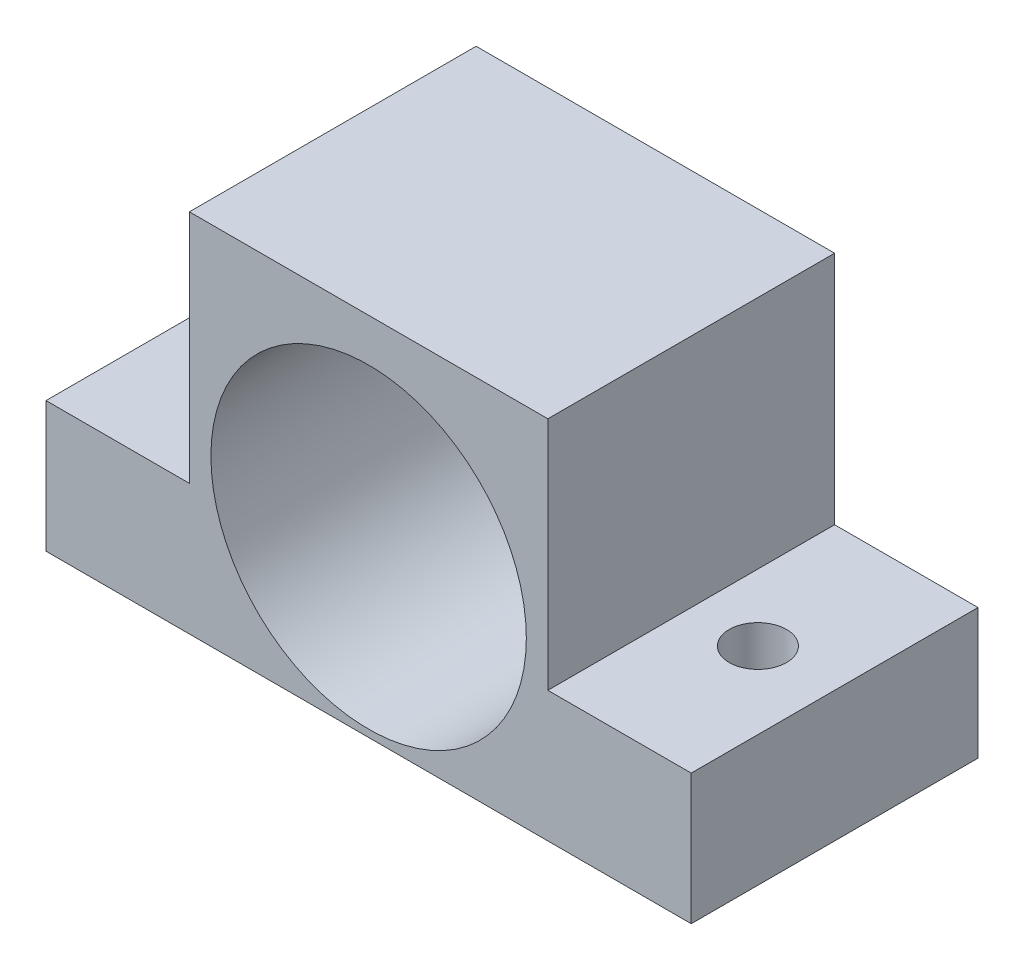
SolidWorks part; units mm, degrees
material "ABS"
ref_plane "Front Plane" through (0, 0, 0) normal (0, 0, 1) x (1, 0, 0)
ref_plane "Top Plane" through (0, 0, 0) normal (0, 1, 0) x (1, 0, 0)
ref_plane "Right Plane" through (0, 0, 0) normal (1, 0, 0) x (0, 0, -1)
sketch "Sketch1" plane through (0, 0, 0) normal (0, 0, 1) x (1, 0, 0)
  line L0 (185.6419, -17.5) -> (-64.3581, -17.5) construction
  line L1 (-11.4483, 8) -> (13.5517, 8)
  line L2 (-11.4483, 8) -> (-11.4483, -17.5)
  line L3 (-11.4483, -17.5) -> (13.5517, -17.5)
  line L4 (13.5517, 8) -> (13.5517, -17.5)
  line L5 (-11.4483, 8) -> (13.5517, -17.5) construction
  line L6 (-11.4483, -17.5) -> (13.5517, 8) construction
  line L7 (13.5517, -17.5) -> (23.5517, -17.5)
  line L8 (13.5517, -17.5) -> (13.5517, -8.4)
  line L9 (13.5517, -8.4) -> (23.5517, -8.4)
  line L10 (23.5517, -17.5) -> (23.5517, -8.4)
  line L11 (13.5517, -17.5) -> (23.5517, -8.4) construction
  line L12 (13.5517, -8.4) -> (23.5517, -17.5) construction
  line L13 (-11.4483, -17.5) -> (-21.4483, -17.5)
  line L14 (-11.4483, -17.5) -> (-11.4483, -8.4)
  line L15 (-11.4483, -8.4) -> (-21.4483, -8.4)
  line L16 (-21.4483, -17.5) -> (-21.4483, -8.4)
  line L17 (-11.4483, -17.5) -> (-21.4483, -8.4) construction
  line L18 (-11.4483, -8.4) -> (-21.4483, -17.5) construction
  circle A0 centre (1.0517, -6) radius 4.1
  circle A1 centre (1.0517, -6) radius 11
  circle A2 centre (1.0517, -6) radius 4 construction
  point P8 (1.0517, -6)
  point P14 (18.5517, -12.95)
  point P16 (-16.4483, -12.95)
  dimension "D4" = 8.2
  dimension "D5" = 22
  dimension "D1" = 14
  dimension "D3" = 25
  dimension "D6" = 10
  dimension "D7" = 9.1
  dimension "D8" = 10
  dimension "D10" = 12.5
extrude "Boss-Extrude1" add sketch "Sketch1" along normal blind 20 contours L4 L1 L2 L3 A1 | L16 L13 L2 L15 | L7 L10 L9 L4 region at (1.0517, 7.6429, 0) region at (-16.4483, -12.95, 0) region at (18.5517, -12.95, 0)
sketch "Sketch2" plane through (0, -8.4, 0) normal (0, 1, 0) x (1, 0, 0)
  line L1 (-11.4483, -20) -> (-21.4483, -20)
  line L4 (23.5517, -20) -> (23.5517, 0)
  circle A0 centre (-16.7988, -10) radius 2
  circle A1 centre (18.2012, -10) radius 2
  circle A2 centre (18.2012, -10) radius 2 construction
  circle A3 centre (-16.7988, -10) radius 2 construction
  dimension "D1" = 4
  dimension "D2" = 4
extrude "Cut-Extrude1" cut sketch "Sketch2" against normal blind 9 contours A0 | A0 | A0 | A0 | A1 region at (-16.7988, -8.4, 10)
